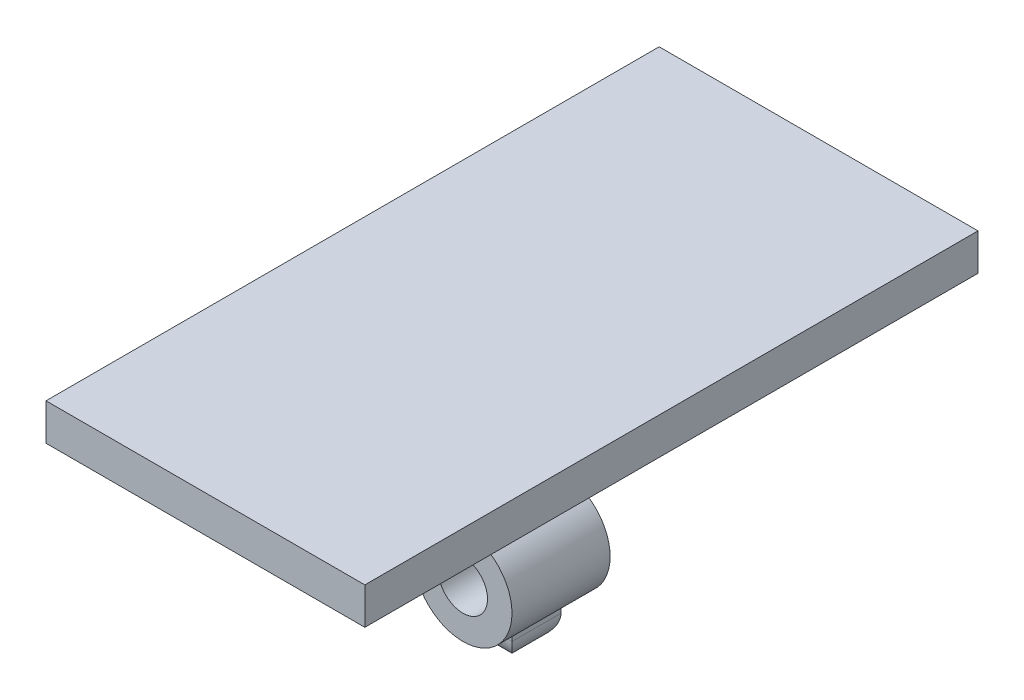
SolidWorks part; units mm, degrees
ref_plane "Front Plane" through (0, 0, 0) normal (0, 0, 1) x (1, 0, 0)
ref_plane "Top Plane" through (0, 0, 0) normal (0, 1, 0) x (1, 0, 0)
ref_plane "Right Plane" through (0, 0, 0) normal (1, 0, 0) x (0, 0, -1)
sketch "Sketch1" plane through (0, 0, 0) normal (0, 0, 1) x (1, 0, 0)
  line L1 (-65, -7.5) -> (65, -7.5)
  line L2 (-65, -7.5) -> (-65, 7.5)
  line L3 (-65, 7.5) -> (65, 7.5)
  line L4 (65, -7.5) -> (65, 7.5)
  line L5 (-65, -7.5) -> (65, 7.5) construction
  line L6 (-65, 7.5) -> (65, -7.5) construction
  point P0 (0, 0)
extrude "Boss-Extrude1" add sketch "Sketch1" along normal blind 250
sketch "Sketch2" plane through (0, -7.5, 0) normal (0, -1, 0) x (1, 0, 0)
  line L0 (0, 250) -> (0, 0) construction
  line L1 (-65, 250) -> (65, 250) construction
  line L3 (-10, 135) -> (10, 135)
  line L4 (-10, 135) -> (-10, 115)
  line L5 (-10, 115) -> (10, 115)
  line L6 (10, 135) -> (10, 115)
  line L7 (-10, 135) -> (10, 115) construction
  line L8 (-10, 115) -> (10, 135) construction
  point P5 (0, 125)
extrude "Boss-Extrude3" add sketch "Sketch2" along normal blind 100
sketch "Sketch3" plane through (0, 0, 135) normal (0, 0, 1) x (1, 0, 0)
  line L0 (0, -7.5) -> (0, -77.5) construction
  line L1 (10, -7.5) -> (-10, -7.5) construction
  circle A0 centre (0, -77.5) radius 10
  circle A1 centre (0, -77.5) radius 20
extrude "Boss-Extrude4" add sketch "Sketch3" along normal blind 10 and the other way blind 30
sketch "Sketch4" plane through (0, 0, 135) normal (0, 0, 1) x (1, 0, 0)
  circle A0 centre (0, -77.5) radius 10
extrude "Cut-Extrude1" cut sketch "Sketch4" against normal through all
fillet "Fillet1" radius 10 4 edges at (0, -107.5, 115) (-10, -107.5, 125) (0, -107.5, 135) (10, -107.5, 125)
